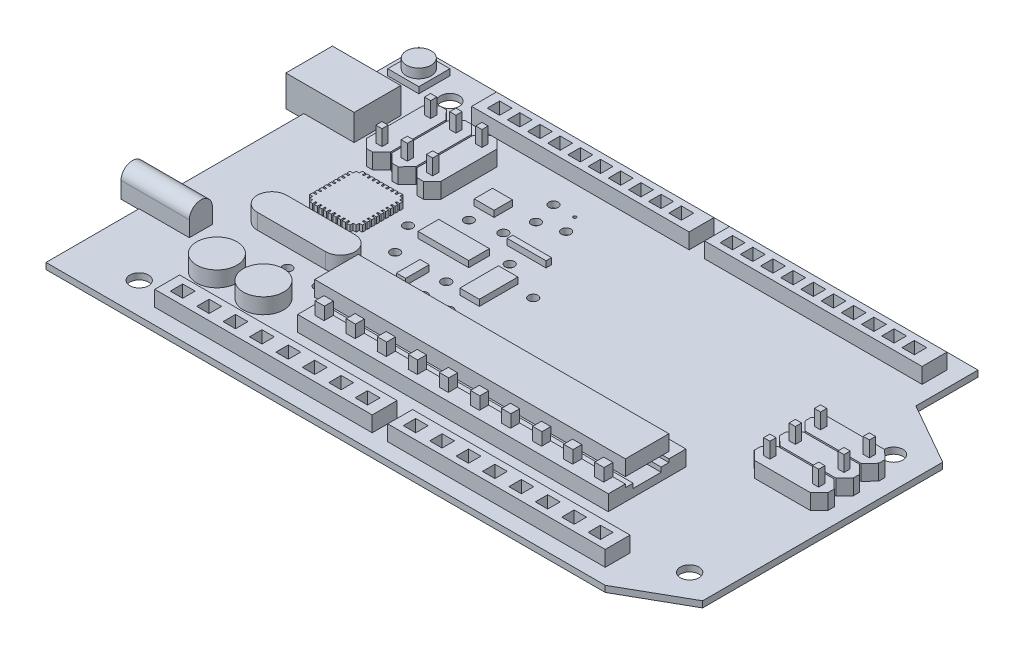
SolidWorks part; units mm, degrees
ref_plane "Front Plane" through (0, 0, 0) normal (0, 0, 1) x (1, 0, 0)
ref_plane "Top Plane" through (0, 0, 0) normal (0, 1, 0) x (1, 0, 0)
ref_plane "Right Plane" through (0, 0, 0) normal (1, 0, 0) x (0, 0, -1)
sketch "Sketch2" plane through (0, 0, 0) normal (0, 1, 0) x (1, 0, 0)
  line L0 (-134.1935, 60.9677) -> (-134.1935, -59.0323)
  line L1 (-134.1935, -59.0323) -> (45.8065, -59.0323)
  line L2 (45.8065, -59.0323) -> (65.8065, -47.6744)
  line L3 (65.8065, -47.6744) -> (65.8065, 29.6099)
  line L4 (65.8065, 29.6099) -> (45.8065, 40.9677)
  line L5 (45.8065, 40.9677) -> (45.8065, 60.9677)
  line L6 (45.8065, 60.9677) -> (-134.1935, 60.9677)
  dimension "D1" = 120
  dimension "D2" = 180
  dimension "D3" = 200
  dimension "D4" = 180
  dimension "D5" = 20
  dimension "D6" = 23
  dimension "D7" = 23
extrude "Boss-Extrude2" add sketch "Sketch2" along normal blind 2
sketch "Sketch3" plane through (0, 2, 0) normal (0, 1, 0) x (1, 0, 0)
  line L0 (-134.1935, 60.9677) -> (-134.1935, -59.0323) construction
  line L1 (-104.1935, 55.9677) -> (-34.1935, 55.9677)
  line L2 (-104.1935, 55.9677) -> (-104.1935, 47.9677)
  line L3 (-104.1935, 47.9677) -> (-34.1935, 47.9677)
  line L4 (-34.1935, 55.9677) -> (-34.1935, 47.9677)
  line L5 (-29.1935, 55.9677) -> (40.8065, 55.9677)
  line L6 (-29.1935, 55.9677) -> (-29.1935, 47.9677)
  line L7 (-29.1935, 47.9677) -> (40.8065, 47.9677)
  line L8 (40.8065, 55.9677) -> (40.8065, 47.9677)
  line L9 (45.8065, 40.9677) -> (45.8065, 60.9677) construction
  line L10 (45.8065, 60.9677) -> (-134.1935, 60.9677) construction
  dimension "D1" = 30
  dimension "D2" = 5
  dimension "D3" = 70
  dimension "D4" = 70
  dimension "D5" = 5
  dimension "D6" = 5
  dimension "D7" = 5
  dimension "D8" = 8
  dimension "D9" = 8
extrude "Boss-Extrude3" add sketch "Sketch3" along normal blind 5
sketch "Sketch4" plane through (0, 7, 0) normal (0, 1, 0) x (1, 0, 0)
  line L0 (-34.1935, 55.9677) -> (-104.1935, 55.9677) construction
  line L1 (-101.1935, 53.9677) -> (-97.1935, 53.9677)
  line L2 (-101.1935, 53.9677) -> (-101.1935, 49.9677)
  line L3 (-101.1935, 49.9677) -> (-97.1935, 49.9677)
  line L4 (-97.1935, 53.9677) -> (-97.1935, 49.9677)
  line L5 (-104.1935, 47.9677) -> (-34.1935, 47.9677) construction
  line L6 (-104.1935, 55.9677) -> (-104.1935, 47.9677) construction
  dimension "D1" = 4
  dimension "D2" = 4
  dimension "D3" = 2
  dimension "D4" = 2
  dimension "D5" = 3
sketch "Sketch5" plane through (0, 7, 0) normal (0, 1, 0) x (1, 0, 0)
  line L0 (40.8065, 55.9677) -> (-29.1935, 55.9677) construction
  line L1 (-26.1935, 53.9677) -> (-22.1935, 53.9677)
  line L2 (-26.1935, 53.9677) -> (-26.1935, 49.9677)
  line L3 (-26.1935, 49.9677) -> (-22.1935, 49.9677)
  line L4 (-22.1935, 53.9677) -> (-22.1935, 49.9677)
  line L5 (-29.1935, 55.9677) -> (-29.1935, 47.9677) construction
  dimension "D1" = 4
  dimension "D2" = 4
  dimension "D3" = 2
  dimension "D4" = 3
extrude "Cut-Extrude1" cut sketch "Sketch4" against normal blind 4
pattern_linear "LPattern3" count 10 spacing 6.5 along (1, 0, 0) of "Cut-Extrude1"
extrude "Cut-Extrude2" cut sketch "Sketch5" against normal blind 4
pattern_linear "LPattern4" count 10 spacing 6.5 along (1, 0, 0) of "Cut-Extrude2"
sketch "Sketch6" plane through (0, 2, 0) normal (0, 1, 0) x (1, 0, 0)
  line L0 (-134.1935, 60.9677) -> (-134.1935, -59.0323) construction
  line L1 (-104.1935, -46.0323) -> (-34.1935, -46.0323)
  line L2 (-104.1935, -46.0323) -> (-104.1935, -54.0323)
  line L3 (-104.1935, -54.0323) -> (-34.1935, -54.0323)
  line L4 (-34.1935, -46.0323) -> (-34.1935, -54.0323)
  line L5 (-29.1935, -46.0323) -> (40.8065, -46.0323)
  line L6 (-29.1935, -46.0323) -> (-29.1935, -54.0323)
  line L7 (-29.1935, -54.0323) -> (40.8065, -54.0323)
  line L8 (40.8065, -46.0323) -> (40.8065, -54.0323)
  line L9 (-134.1935, -59.0323) -> (45.8065, -59.0323) construction
  point P11 (-29.1935, -50.0323)
  dimension "D1" = 5
  dimension "D2" = 70
  dimension "D3" = 70
  dimension "D4" = 30
  dimension "D5" = 5
  dimension "D6" = 5
  dimension "D7" = 5
  dimension "D8" = 8
  dimension "D9" = 8
extrude "Boss-Extrude7" add sketch "Sketch6" along normal blind 5
sketch "Sketch7" plane through (0, 7, 0) normal (0, 1, 0) x (1, 0, 0)
  line L0 (-104.1935, -54.0323) -> (-34.1935, -54.0323) construction
  line L1 (-101.1935, -48.0323) -> (-97.1935, -48.0323)
  line L2 (-101.1935, -48.0323) -> (-101.1935, -52.0323)
  line L3 (-101.1935, -52.0323) -> (-97.1935, -52.0323)
  line L4 (-97.1935, -48.0323) -> (-97.1935, -52.0323)
  line L5 (-34.1935, -46.0323) -> (-104.1935, -46.0323) construction
  line L6 (-104.1935, -46.0323) -> (-104.1935, -54.0323) construction
  dimension "D1" = 4
  dimension "D2" = 4
  dimension "D3" = 2
  dimension "D4" = 2
  dimension "D5" = 3
extrude "Cut-Extrude3" cut sketch "Sketch7" against normal blind 4
pattern_linear "LPattern5" count 8 spacing 8.5 along (1, 0, 0) of "Cut-Extrude3"
sketch "Sketch8" plane through (0, 7, 0) normal (0, 1, 0) x (1, 0, 0)
  line L0 (-29.1935, -54.0323) -> (40.8065, -54.0323) construction
  line L1 (-26.1935, -48.0323) -> (-22.1935, -48.0323)
  line L2 (-26.1935, -48.0323) -> (-26.1935, -52.0323)
  line L3 (-26.1935, -52.0323) -> (-22.1935, -52.0323)
  line L4 (-22.1935, -48.0323) -> (-22.1935, -52.0323)
  line L5 (-29.1935, -46.0323) -> (-29.1935, -54.0323) construction
  dimension "D1" = 4
  dimension "D2" = 4
  dimension "D3" = 2
  dimension "D4" = 3
extrude "Cut-Extrude4" cut sketch "Sketch8" against normal blind 4
pattern_linear "LPattern6" count 8 spacing 8.5 along (1, 0, 0) of "Cut-Extrude4"
sketch "Sketch9" plane through (0, 2, 0) normal (0, 1, 0) x (1, 0, 0)
  line L0 (65.8065, -47.6744) -> (65.8065, 29.6099) construction
  line L1 (-104.1935, -46.0323) -> (-104.1935, -54.0323) construction
  line L2 (-104.1935, 55.9677) -> (-104.1935, 47.9677) construction
  line L3 (45.8065, 60.9677) -> (-134.1935, 60.9677) construction
  line L4 (-134.1935, -59.0323) -> (45.8065, -59.0323) construction
  line L5 (65.8065, 29.6099) -> (45.8065, 40.9677) construction
  line L6 (45.8065, -59.0323) -> (65.8065, -47.6744) construction
  circle A0 centre (55.8065, 23.7888) radius 3
  circle A1 centre (55.8065, -41.8533) radius 3
  circle A2 centre (-114.1935, 50.9677) radius 3
  circle A3 centre (-114.1935, -49.0323) radius 3
  dimension "D1" = 6
  dimension "D2" = 6
  dimension "D3" = 6
  dimension "D4" = 6
  dimension "D5" = 10
  dimension "D9" = 10
  dimension "D10" = 10
  dimension "D11" = 10
  dimension "D6" = 10
  dimension "D7" = 10
  dimension "D8" = 10
  dimension "D12" = 10
extrude "Cut-Extrude5" cut sketch "Sketch9" against normal blind 4
sketch "Sketch10" plane through (0, 2, 0) normal (0, 1, 0) x (1, 0, 0)
  line L0 (65.8065, -47.6744) -> (65.8065, 29.6099) construction
  line L1 (-74.1935, -13.0323) -> (25.8065, -13.0323)
  line L2 (-74.1935, -13.0323) -> (-74.1935, -38.0323)
  line L3 (-74.1935, -38.0323) -> (25.8065, -38.0323)
  line L4 (25.8065, -13.0323) -> (25.8065, -38.0323)
  line L5 (40.8065, -46.0323) -> (-29.1935, -46.0323) construction
  dimension "D1" = 40
  dimension "D2" = 8
  dimension "D3" = 25
  dimension "D4" = 100
extrude "Boss-Extrude8" add sketch "Sketch10" along normal blind 5
sketch "Sketch11" plane through (25.8065, 0, 0) normal (1, 0, 0) x (0, 0, -1)
  line L0 (-38.0323, 7) -> (-13.0323, 7) construction
  line L1 (-21.0323, 7) -> (-30.0323, 7)
  line L2 (-21.0323, 7) -> (-21.0323, 4.5)
  line L3 (-21.0323, 4.5) -> (-30.0323, 4.5)
  line L4 (-30.0323, 7) -> (-30.0323, 4.5)
  line L5 (-13.0323, 7) -> (-13.0323, 2) construction
  line L6 (-38.0323, 7) -> (-38.0323, 2) construction
  line L7 (-38.0323, 2) -> (-13.0323, 2) construction
  dimension "D1" = 8
  dimension "D2" = 9
  dimension "D3" = 8
  dimension "D4" = 2.5
  dimension "D5" = 2.5
extrude "Cut-Extrude6" cut sketch "Sketch11" against normal blind 100
sketch "Sketch13" plane through (0, 7, 0) normal (0, 1, 0) x (1, 0, 0)
  line L0 (-74.1935, -13.0323) -> (-74.1935, -21.0323) construction
  line L1 (-71.1935, -15.5323) -> (-68.1935, -15.5323)
  line L2 (-71.1935, -15.5323) -> (-71.1935, -18.5323)
  line L3 (-71.1935, -18.5323) -> (-68.1935, -18.5323)
  line L4 (-68.1935, -15.5323) -> (-68.1935, -18.5323)
  line L5 (-71.1935, -32.5323) -> (-68.1935, -32.5323)
  line L6 (-71.1935, -32.5323) -> (-71.1935, -35.5323)
  line L7 (-71.1935, -35.5323) -> (-68.1935, -35.5323)
  line L8 (-68.1935, -32.5323) -> (-68.1935, -35.5323)
  line L9 (-74.1935, -30.0323) -> (-74.1935, -38.0323) construction
  line L10 (-74.1935, -21.0323) -> (25.8065, -21.0323) construction
  line L11 (25.8065, -13.0323) -> (-74.1935, -13.0323) construction
  line L12 (-74.1935, -30.0323) -> (25.8065, -30.0323) construction
  dimension "D1" = 3
  dimension "D2" = 3
  dimension "D3" = 3
  dimension "D4" = 3
  dimension "D5" = 3
  dimension "D6" = 3
  dimension "D7" = 2.5
  dimension "D8" = 2.5
  dimension "D9" = 2.5
extrude "Cut-Extrude7" cut sketch "Sketch13" against normal blind 4
pattern_linear "LPattern7" count 10 spacing 10 along (1, 0, 0) of "Cut-Extrude7"
sketch "Sketch15" plane through (0, 3, 0) normal (0, 1, 0) x (1, 0, 0)
  line L0 (-68.1935, -18.5323) -> (-68.1935, -15.5323) construction
  line L1 (-71.1935, -15.5323) -> (-68.1935, -15.5323)
  line L2 (-71.1935, -15.5323) -> (-71.1935, -18.5323)
  line L3 (-71.1935, -18.5323) -> (-68.1935, -18.5323)
  line L4 (-68.1935, -15.5323) -> (-68.1935, -18.5323)
  line L5 (-71.1935, -18.5323) -> (-68.1935, -18.5323) construction
  line L6 (-68.1935, -35.5323) -> (-68.1935, -32.5323) construction
  line L7 (-71.1935, -32.5323) -> (-68.1935, -32.5323)
  line L8 (-71.1935, -32.5323) -> (-71.1935, -35.4)
  line L9 (-71.1935, -35.4) -> (-68.1935, -35.4)
  line L10 (-68.1935, -32.5323) -> (-68.1935, -35.4)
extrude "Boss-Extrude9" add sketch "Sketch15" along normal blind 8
pattern_linear "LPattern8" count 10 spacing 10 along (1, 0, 0) of "Boss-Extrude9"
sketch "Sketch17" plane through (0, 7, 0) normal (0, 1, 0) x (1, 0, 0)
  line L0 (-74.1935, -13.0323) -> (-74.1935, -21.0323) construction
  line L1 (-74.1935, -18.5318) -> (25.8065, -18.5318)
  line L2 (-74.1935, -18.5318) -> (-74.1935, -32.5436)
  line L3 (-74.1935, -32.5436) -> (25.8065, -32.5436)
  line L4 (25.8065, -18.5318) -> (25.8065, -32.5436)
  line L5 (25.8065, -38.0323) -> (25.8065, -30.0323) construction
extrude "Boss-Extrude10" add sketch "Sketch17" along normal blind 7 and the other way blind 1
sketch "Sketch18" plane through (25.8065, 0, 0) normal (1, 0, 0) x (0, 0, -1)
  line L0 (-18.5318, 7) -> (-18.5318, 14) construction
  line L1 (-18.5318, 9.0392) -> (-32.5598, 9.0392)
  line L2 (-18.5318, 9.0392) -> (-18.5318, 5.9657)
  line L3 (-18.5318, 5.9657) -> (-32.5598, 5.9657)
  line L4 (-32.5598, 9.0392) -> (-32.5598, 5.9657)
extrude "Cut-Extrude8" cut sketch "Sketch18" against normal blind 100
sketch "Sketch20" plane through (0, 2, 0) normal (0, 1, 0) x (1, 0, 0)
  line L0 (39.9288, 18.7888) -> (57.9288, 18.7888)
  line L1 (57.9288, 18.7888) -> (60.8065, 16.0105)
  line L2 (60.8065, 16.0105) -> (60.8065, 14.0105)
  line L3 (60.8065, 14.0105) -> (58.0281, 11.1329)
  line L4 (58.0281, 11.1329) -> (40.0281, 11.1329)
  line L5 (40.0281, 11.1329) -> (37.1505, 13.9112)
  line L6 (37.1505, 13.9112) -> (37.1505, 15.9112)
  line L7 (37.1505, 15.9112) -> (39.9288, 18.7888)
  line L8 (65.8065, -47.6744) -> (65.8065, 29.6099) construction
  line L9 (39.9288, 10.6329) -> (57.9288, 10.6329)
  line L10 (57.9288, 10.6329) -> (60.8065, 7.8545)
  line L11 (60.8065, 7.8545) -> (60.8065, 5.8545)
  line L12 (60.8065, 5.8545) -> (58.0281, 2.9769)
  line L13 (58.0281, 2.9769) -> (40.0281, 2.9769)
  line L14 (40.0281, 2.9769) -> (37.1505, 5.7552)
  line L15 (37.1505, 5.7552) -> (37.1505, 7.7552)
  line L16 (37.1505, 7.7552) -> (39.9288, 10.6329)
  line L17 (39.9288, 2.4769) -> (57.9288, 2.4769)
  line L18 (57.9288, 2.4769) -> (60.8065, -0.3015)
  line L19 (60.8065, -0.3015) -> (60.8065, -2.3015)
  line L20 (60.8065, -2.3015) -> (58.0281, -5.1791)
  line L21 (58.0281, -5.1791) -> (40.0281, -5.1791)
  line L22 (40.0281, -5.1791) -> (37.1505, -2.4008)
  line L23 (37.1505, -2.4008) -> (37.1505, -0.4008)
  line L24 (37.1505, -0.4008) -> (39.9288, 2.4769)
  circle A0 centre (55.8065, 23.7888) radius 3 construction
  dimension "D2" = 5
  dimension "D1" = 5
  dimension "D3" = 18
  dimension "D4" = 4
  dimension "D5" = 4
  dimension "D6" = 4
  dimension "D7" = 18
  dimension "D8" = 4
  dimension "D9" = 2
  dimension "D10" = 2
  dimension "D11" = 5
  dimension "D12" = 5
  dimension "D13" = 0.5
  dimension "D14" = 0.5
  dimension "D15" = 4
  dimension "D16" = 4
  dimension "D17" = 2
  dimension "D18" = 2
  dimension "D19" = 4
  dimension "D20" = 4
  dimension "D21" = 18
  dimension "D22" = 4
  dimension "D23" = 4
  dimension "D24" = 2
  dimension "D25" = 4
  dimension "D26" = 4
  dimension "D27" = 2
  dimension "D28" = 18
  dimension "D29" = 18
  dimension "D30" = 18
extrude "Boss-Extrude13" add sketch "Sketch20" along normal blind 5
sketch "Sketch21" plane through (0, 7, 0) normal (0, 1, 0) x (1, 0, 0)
  line L0 (37.1505, -0.4008) -> (37.1505, -2.4008) construction
  line L1 (40.1505, 15.9388) -> (42.1505, 15.9388)
  line L2 (40.1505, 15.9388) -> (40.1505, 13.9388)
  line L3 (40.1505, 13.9388) -> (42.1505, 13.9388)
  line L4 (42.1505, 15.9388) -> (42.1505, 13.9388)
  line L5 (40.1505, 7.8329) -> (42.1505, 7.8329)
  line L6 (40.1505, 7.8329) -> (40.1505, 5.8329)
  line L7 (40.1505, 5.8329) -> (42.1505, 5.8329)
  line L8 (42.1505, 7.8329) -> (42.1505, 5.8329)
  line L9 (40.1505, -0.3699) -> (42.1505, -0.3699)
  line L10 (40.1505, -0.3699) -> (40.1505, -2.3699)
  line L11 (40.1505, -2.3699) -> (42.1505, -2.3699)
  line L12 (42.1505, -0.3699) -> (42.1505, -2.3699)
  line L13 (55.8065, 15.9888) -> (57.8065, 15.9888)
  line L14 (55.8065, 15.9888) -> (55.8065, 13.9888)
  line L15 (55.8065, 13.9888) -> (57.8065, 13.9888)
  line L16 (57.8065, 15.9888) -> (57.8065, 13.9888)
  line L17 (55.8065, 7.8329) -> (57.8065, 7.8329)
  line L18 (55.8065, 7.8329) -> (55.8065, 5.8329)
  line L19 (55.8065, 5.8329) -> (57.8065, 5.8329)
  line L20 (57.8065, 7.8329) -> (57.8065, 5.8329)
  line L21 (55.8065, -0.3231) -> (57.8065, -0.3231)
  line L22 (55.8065, -0.3231) -> (55.8065, -2.3231)
  line L23 (55.8065, -2.3231) -> (57.8065, -2.3231)
  line L24 (57.8065, -0.3231) -> (57.8065, -2.3231)
  line L25 (37.1505, 7.7552) -> (37.1505, 5.7552) construction
  line L26 (37.1505, 15.9112) -> (37.1505, 13.9112) construction
  line L27 (60.8065, 14.0105) -> (60.8065, 16.0105) construction
  line L28 (60.8065, 5.8545) -> (60.8065, 7.8545) construction
  line L29 (60.8065, -2.3015) -> (60.8065, -0.3015) construction
  line L30 (57.9288, 2.4769) -> (39.9288, 2.4769) construction
  line L31 (57.9288, 2.4769) -> (39.9288, 2.4769) construction
  line L32 (40.0281, -5.1791) -> (58.0281, -5.1791) construction
  line L33 (57.9288, 18.7888) -> (39.9288, 18.7888) construction
  line L34 (40.0281, 11.1329) -> (58.0281, 11.1329) construction
  line L35 (57.9288, 18.7888) -> (39.9288, 18.7888) construction
  line L36 (57.9288, 10.6329) -> (39.9288, 10.6329) construction
  point P36 (41.1505, -0.3699)
  dimension "D1" = 2
  dimension "D2" = 2
  dimension "D3" = 2
  dimension "D4" = 2
  dimension "D5" = 2
  dimension "D6" = 2
  dimension "D7" = 2
  dimension "D8" = 2
  dimension "D9" = 2
  dimension "D10" = 2
  dimension "D11" = 2
  dimension "D12" = 3
  dimension "D13" = 3
  dimension "D14" = 3
  dimension "D15" = 2
  dimension "D16" = 3
  dimension "D17" = 3
  dimension "D18" = 3
  dimension "D19" = 2.8468
  dimension "D20" = 2.8468
  dimension "D21" = 2.8092
  dimension "D22" = 2.85
  dimension "D23" = 2.806
  dimension "D24" = 2.8
  dimension "D25" = 2.8
  dimension "D26" = 2.8
  dimension "D27" = 2.8
extrude "Boss-Extrude14" add sketch "Sketch21" along normal blind 5
sketch "Sketch22" plane through (0, 2, 0) normal (0, 1, 0) x (1, 0, 0)
  line L0 (-112.1935, 40.1574) -> (-112.1935, 22.1574)
  line L1 (-112.1935, 22.1574) -> (-109.3832, 19.311)
  line L2 (-109.3832, 19.311) -> (-107.3832, 19.311)
  line L3 (-107.3832, 19.311) -> (-104.5368, 22.1213)
  line L4 (-104.5368, 22.1213) -> (-104.5368, 40.1213)
  line L5 (-104.5368, 40.1213) -> (-107.3471, 42.9677)
  line L6 (-107.3471, 42.9677) -> (-109.3471, 42.9677)
  line L7 (-109.3471, 42.9677) -> (-112.1935, 40.1574)
  line L8 (-104.1935, 47.9677) -> (-34.1935, 47.9677) construction
  line L9 (-134.1935, 60.9677) -> (-134.1935, -59.0323) construction
  line L10 (-104.0368, 40.0944) -> (-104.0368, 22.0944)
  line L11 (-104.0368, 22.0944) -> (-101.1634, 19.3116)
  line L12 (-101.1634, 19.3116) -> (-99.1634, 19.3116)
  line L13 (-99.1634, 19.3116) -> (-96.3807, 22.185)
  line L14 (-96.3807, 22.185) -> (-96.3807, 40.185)
  line L15 (-96.3807, 40.185) -> (-99.2541, 42.9677)
  line L16 (-99.2541, 42.9677) -> (-101.2541, 42.9677)
  line L17 (-101.2541, 42.9677) -> (-104.0368, 40.0944)
  line L18 (-95.8807, 40.1242) -> (-95.8807, 22.1242)
  line L19 (-95.8807, 22.1242) -> (-93.0371, 19.311)
  line L20 (-93.0371, 19.311) -> (-91.0371, 19.311)
  line L21 (-91.0371, 19.311) -> (-88.2239, 22.1545)
  line L22 (-88.2239, 22.1545) -> (-88.2239, 40.1545)
  line L23 (-88.2239, 40.1545) -> (-91.0675, 42.9677)
  line L24 (-91.0675, 42.9677) -> (-93.0675, 42.9677)
  line L25 (-93.0675, 42.9677) -> (-95.8807, 40.1242)
  dimension "D1" = 5
  dimension "D2" = 22
  dimension "D3" = 18
  dimension "D4" = 18
  dimension "D5" = 4
  dimension "D6" = 4
  dimension "D7" = 4
  dimension "D8" = 4
  dimension "D9" = 2
  dimension "D10" = 2
  dimension "D11" = 5
  dimension "D12" = 5
  dimension "D13" = 0.5
  dimension "D14" = 0.5
  dimension "D15" = 4
  dimension "D16" = 4
  dimension "D17" = 4
  dimension "D18" = 4
  dimension "D19" = 4
  dimension "D20" = 18
  dimension "D21" = 18
  dimension "D22" = 4
  dimension "D23" = 18
  dimension "D24" = 18
  dimension "D25" = 4
  dimension "D26" = 4
  dimension "D27" = 2
  dimension "D28" = 2
  dimension "D29" = 2
extrude "Boss-Extrude15" add sketch "Sketch22" along normal blind 5
sketch "Sketch23" plane through (0, 7, 0) normal (0, 1, 0) x (1, 0, 0)
  line L0 (-107.3471, 42.9677) -> (-109.3471, 42.9677) construction
  line L1 (-109.3935, 39.9677) -> (-107.3935, 39.9677)
  line L2 (-109.3935, 39.9677) -> (-109.3935, 37.9677)
  line L3 (-109.3935, 37.9677) -> (-107.3935, 37.9677)
  line L4 (-107.3935, 39.9677) -> (-107.3935, 37.9677)
  line L5 (-101.2368, 39.9677) -> (-99.2368, 39.9677)
  line L6 (-101.2368, 39.9677) -> (-101.2368, 37.9677)
  line L7 (-101.2368, 37.9677) -> (-99.2368, 37.9677)
  line L8 (-99.2368, 39.9677) -> (-99.2368, 37.9677)
  line L9 (-93.0807, 40.1677) -> (-91.0807, 40.1677)
  line L10 (-93.0807, 40.1677) -> (-93.0807, 38.1677)
  line L11 (-93.0807, 38.1677) -> (-91.0807, 38.1677)
  line L12 (-91.0807, 40.1677) -> (-91.0807, 38.1677)
  line L13 (-93.0807, 24.311) -> (-91.0807, 24.311)
  line L14 (-93.0807, 24.311) -> (-93.0807, 22.311)
  line L15 (-93.0807, 22.311) -> (-91.0807, 22.311)
  line L16 (-91.0807, 24.311) -> (-91.0807, 22.311)
  line L17 (-101.2368, 24.3116) -> (-99.2368, 24.3116)
  line L18 (-101.2368, 24.3116) -> (-101.2368, 22.3116)
  line L19 (-101.2368, 22.3116) -> (-99.2368, 22.3116)
  line L20 (-99.2368, 24.3116) -> (-99.2368, 22.3116)
  line L21 (-109.3935, 24.311) -> (-107.3935, 24.311)
  line L22 (-109.3935, 24.311) -> (-109.3935, 22.311)
  line L23 (-109.3935, 22.311) -> (-107.3935, 22.311)
  line L24 (-107.3935, 24.311) -> (-107.3935, 22.311)
  line L25 (-112.1935, 40.1574) -> (-112.1935, 22.1574) construction
  line L26 (-104.5368, 22.1213) -> (-104.5368, 40.1213) construction
  line L27 (-99.2541, 42.9677) -> (-101.2541, 42.9677) construction
  line L28 (-104.0368, 40.0944) -> (-104.0368, 22.0944) construction
  line L29 (-95.8807, 40.1242) -> (-95.8807, 22.1242) construction
  line L30 (-91.0675, 42.9677) -> (-93.0675, 42.9677) construction
  line L31 (-109.3832, 19.311) -> (-107.3832, 19.311) construction
  line L32 (-101.1634, 19.3116) -> (-99.1634, 19.3116) construction
  line L33 (-93.0371, 19.311) -> (-91.0371, 19.311) construction
  dimension "D1" = 2
  dimension "D2" = 2
  dimension "D3" = 3
  dimension "D4" = 2.8
  dimension "D5" = 2.8567
  dimension "D6" = 2
  dimension "D7" = 2
  dimension "D8" = 3
  dimension "D9" = 2.8
  dimension "D10" = 2
  dimension "D11" = 2
  dimension "D12" = 2.8
  dimension "D13" = 2.8
  dimension "D14" = 2
  dimension "D15" = 2
  dimension "D16" = 3
  dimension "D17" = 2.8
  dimension "D18" = 2
  dimension "D19" = 2.8
  dimension "D20" = 2
  dimension "D21" = 3
  dimension "D22" = 2.8
  dimension "D23" = 2
  dimension "D24" = 2
  dimension "D25" = 3
extrude "Boss-Extrude16" add sketch "Sketch23" along normal blind 5
sketch "Sketch24" plane through (0, 2, 0) normal (0, 1, 0) x (1, 0, 0)
  line L0 (-101.1634, 19.3116) -> (-99.1634, 19.3116) construction
  line L1 (-107.6935, 14.3116) -> (-92.6935, 14.3116)
  line L2 (-107.6935, 14.3116) -> (-107.6935, -0.6884)
  line L3 (-107.6935, -0.6884) -> (-92.6935, -0.6884)
  line L4 (-92.6935, 14.3116) -> (-92.6935, -0.6884)
  line L5 (-134.1935, 60.9677) -> (-134.1935, -59.0323) construction
  dimension "D1" = 5
  dimension "D2" = 26.5
  dimension "D3" = 15
  dimension "D4" = 15
extrude "Boss-Extrude17" add sketch "Sketch24" along normal blind 2
sketch "Sketch26" plane through (0, 2, 0) normal (0, 1, 0) x (1, 0, 0)
  line L0 (-92.6935, 14.3116) -> (-107.6935, 14.3116) construction
  line L1 (-106.6935, 14.3116) -> (-105.6935, 14.3116)
  line L2 (-106.6935, 14.3116) -> (-106.6935, 15.3116)
  line L3 (-106.6935, 15.3116) -> (-105.6935, 15.3116)
  line L4 (-105.6935, 14.3116) -> (-105.6935, 15.3116)
  dimension "D1" = 1
  dimension "D2" = 1
  dimension "D3" = 1
extrude "Boss-Extrude19" add sketch "Sketch26" along normal blind 2
pattern_linear "LPattern9" count 9 spacing 1.5 along (1, 0, 0) of "Boss-Extrude19"
sketch "Sketch27" plane through (0, 2, 0) normal (0, 1, 0) x (1, 0, 0)
  line L0 (-107.6935, -0.6884) -> (-92.6935, -0.6884) construction
  line L1 (-106.6935, -0.6884) -> (-105.6935, -0.6884)
  line L2 (-106.6935, -0.6884) -> (-106.6935, -1.6884)
  line L3 (-106.6935, -1.6884) -> (-105.6935, -1.6884)
  line L4 (-105.6935, -0.6884) -> (-105.6935, -1.6884)
  dimension "D1" = 1
  dimension "D2" = 1
  dimension "D3" = 1
extrude "Boss-Extrude20" add sketch "Sketch27" along normal blind 2
pattern_linear "LPattern10" count 9 spacing 1.5 along (1, 0, 0) of "Boss-Extrude20"
sketch "Sketch28" plane through (0, 2, 0) normal (0, 1, 0) x (1, 0, 0)
  line L0 (-92.6935, -0.6884) -> (-92.6935, 14.3116) construction
  line L1 (-92.6935, 13.3116) -> (-91.6935, 13.3116)
  line L2 (-92.6935, 13.3116) -> (-92.6935, 12.3116)
  line L3 (-92.6935, 12.3116) -> (-91.6935, 12.3116)
  line L4 (-91.6935, 13.3116) -> (-91.6935, 12.3116)
  line L5 (-92.6935, 11.8116) -> (-92.6935, 10.8116)
  line L6 (-92.6935, 11.8116) -> (-91.6935, 11.8116)
  line L7 (-91.6935, 11.8116) -> (-91.6935, 10.8116)
  line L8 (-92.6935, 10.8116) -> (-91.6935, 10.8116)
  line L9 (-92.6935, 10.3116) -> (-92.6935, 9.3116)
  line L10 (-92.6935, 10.3116) -> (-91.6935, 10.3116)
  line L11 (-91.6935, 10.3116) -> (-91.6935, 9.3116)
  line L12 (-92.6935, 9.3116) -> (-91.6935, 9.3116)
  line L13 (-92.6935, 8.8116) -> (-92.6935, 7.8116)
  line L14 (-92.6935, 8.8116) -> (-91.6935, 8.8116)
  line L15 (-91.6935, 8.8116) -> (-91.6935, 7.8116)
  line L16 (-92.6935, 7.8116) -> (-91.6935, 7.8116)
  line L17 (-92.6935, 7.3116) -> (-92.6935, 6.3116)
  line L18 (-92.6935, 7.3116) -> (-91.6935, 7.3116)
  line L19 (-91.6935, 7.3116) -> (-91.6935, 6.3116)
  line L20 (-92.6935, 6.3116) -> (-91.6935, 6.3116)
  line L21 (-92.6935, 5.8116) -> (-92.6935, 4.8116)
  line L22 (-92.6935, 5.8116) -> (-91.6935, 5.8116)
  line L23 (-91.6935, 5.8116) -> (-91.6935, 4.8116)
  line L24 (-92.6935, 4.8116) -> (-91.6935, 4.8116)
  line L25 (-92.6935, 4.3116) -> (-92.6935, 3.3116)
  line L26 (-92.6935, 4.3116) -> (-91.6935, 4.3116)
  line L27 (-91.6935, 4.3116) -> (-91.6935, 3.3116)
  line L28 (-92.6935, 3.3116) -> (-91.6935, 3.3116)
  line L29 (-92.6935, 2.8116) -> (-92.6935, 1.8116)
  line L30 (-92.6935, 2.8116) -> (-91.6935, 2.8116)
  line L31 (-91.6935, 2.8116) -> (-91.6935, 1.8116)
  line L32 (-92.6935, 1.8116) -> (-91.6935, 1.8116)
  line L33 (-92.6935, 1.3116) -> (-92.6935, 0.3116)
  line L34 (-92.6935, 1.3116) -> (-91.6935, 1.3116)
  line L35 (-91.6935, 1.3116) -> (-91.6935, 0.3116)
  line L36 (-92.6935, 0.3116) -> (-91.6935, 0.3116)
  dimension "D1" = 1
  dimension "D2" = 1
  dimension "D3" = 1
  dimension "D4" = 9
extrude "Boss-Extrude24" add sketch "Sketch28" along normal blind 2
sketch "Sketch31" plane through (0, 2, 0) normal (0, 1, 0) x (1, 0, 0)
  line L0 (-107.6935, 14.3116) -> (-107.6935, -0.6884) construction
  line L1 (-107.6935, 13.3116) -> (-108.6935, 13.3116)
  line L2 (-107.6935, 13.3116) -> (-107.6935, 12.3116)
  line L3 (-107.6935, 12.3116) -> (-108.6935, 12.3116)
  line L4 (-108.6935, 13.3116) -> (-108.6935, 12.3116)
  line L5 (-107.6935, 11.8116) -> (-107.6935, 10.8116)
  line L6 (-107.6935, 11.8116) -> (-108.6935, 11.8116)
  line L7 (-108.6935, 11.8116) -> (-108.6935, 10.8116)
  line L8 (-107.6935, 10.8116) -> (-108.6935, 10.8116)
  line L9 (-107.6935, 10.3116) -> (-107.6935, 9.3116)
  line L10 (-107.6935, 10.3116) -> (-108.6935, 10.3116)
  line L11 (-108.6935, 10.3116) -> (-108.6935, 9.3116)
  line L12 (-107.6935, 9.3116) -> (-108.6935, 9.3116)
  line L13 (-107.6935, 8.8116) -> (-107.6935, 7.8116)
  line L14 (-107.6935, 8.8116) -> (-108.6935, 8.8116)
  line L15 (-108.6935, 8.8116) -> (-108.6935, 7.8116)
  line L16 (-107.6935, 7.8116) -> (-108.6935, 7.8116)
  line L17 (-107.6935, 7.3116) -> (-107.6935, 6.3116)
  line L18 (-107.6935, 7.3116) -> (-108.6935, 7.3116)
  line L19 (-108.6935, 7.3116) -> (-108.6935, 6.3116)
  line L20 (-107.6935, 6.3116) -> (-108.6935, 6.3116)
  line L21 (-107.6935, 5.8116) -> (-107.6935, 4.8116)
  line L22 (-107.6935, 5.8116) -> (-108.6935, 5.8116)
  line L23 (-108.6935, 5.8116) -> (-108.6935, 4.8116)
  line L24 (-107.6935, 4.8116) -> (-108.6935, 4.8116)
  line L25 (-107.6935, 4.3116) -> (-107.6935, 3.3116)
  line L26 (-107.6935, 4.3116) -> (-108.6935, 4.3116)
  line L27 (-108.6935, 4.3116) -> (-108.6935, 3.3116)
  line L28 (-107.6935, 3.3116) -> (-108.6935, 3.3116)
  line L29 (-107.6935, 2.8116) -> (-107.6935, 1.8116)
  line L30 (-107.6935, 2.8116) -> (-108.6935, 2.8116)
  line L31 (-108.6935, 2.8116) -> (-108.6935, 1.8116)
  line L32 (-107.6935, 1.8116) -> (-108.6935, 1.8116)
  line L33 (-107.6935, 1.3116) -> (-107.6935, 0.3116)
  line L34 (-107.6935, 1.3116) -> (-108.6935, 1.3116)
  line L35 (-108.6935, 1.3116) -> (-108.6935, 0.3116)
  line L36 (-107.6935, 0.3116) -> (-108.6935, 0.3116)
  dimension "D1" = 1
  dimension "D2" = 1
  dimension "D3" = 1
  dimension "D4" = 9
extrude "Boss-Extrude25" add sketch "Sketch31" along normal blind 2
ref_plane "Plane1" through (-120, 0, 0) normal (1, 0, 0) x (0, 0, -1)
sketch "Sketch33" plane through (-120, 0, 0) normal (1, 0, 0) x (0, 0, -1)
  line L0 (-21.6825, 1.7444) -> (-21.6825, 6.993)
  line L1 (-29.0806, 1.7444) -> (-29.0806, 6.993)
  line L2 (-21.6825, 1.7444) -> (-29.0806, 1.7444)
  arc A0 (-29.0806, 6.993) -> (-21.6825, 6.993) centre (-25.3816, 6.993) cw
extrude "Boss-Extrude26" add sketch "Sketch33" along normal blind 2 and the other way blind 20
sketch "Sketch34" plane through (-140, 0, 0) normal (-1, 0, 0) x (0, 0, 1)
  line L0 (22.8825, 3.2444) -> (27.8806, 3.2444)
  line L1 (27.8806, 3.2444) -> (27.8806, 6.9876)
  line L2 (22.8825, 3.2444) -> (22.8825, 6.9876)
  line L3 (29.0806, 1.7444) -> (21.6825, 1.7444) construction
  line L4 (21.6825, 1.7444) -> (21.6825, 6.993) construction
  line L5 (29.0806, 6.993) -> (29.0806, 1.7444) construction
  arc A0 (22.8825, 6.9876) -> (27.8806, 6.9876) centre (25.3816, 6.9876) cw
  dimension "D2" = 1.2
  dimension "D1" = 1.5
  dimension "D3" = 3.7432
  dimension "D4" = 1.2
  dimension "D5" = 4.9981
extrude "Cut-Extrude9" cut sketch "Sketch34" against normal blind 15
sketch "Sketch35" plane through (-120, 0, 0) normal (1, 0, 0) x (0, 0, -1)
  line L1 (38.9677, 0.4127) -> (23.9677, 0.4127)
  line L2 (38.9677, 0.4127) -> (38.9677, 10.4127)
  line L3 (38.9677, 10.4127) -> (23.9677, 10.4127)
  line L4 (23.9677, 0.4127) -> (23.9677, 10.4127)
  dimension "D1" = 10
  dimension "D2" = 15
  dimension "D3" = 22
extrude "Boss-Extrude27" add sketch "Sketch35" along normal blind 2 and the other way blind 20
sketch "Sketch36" plane through (-140, 0, 0) normal (-1, 0, 0) x (0, 0, 1)
  line L0 (-35.4677, 1.9127) -> (-27.4677, 1.9127)
  line L1 (-27.4677, 1.9127) -> (-27.4677, 6.5503)
  line L2 (-27.4677, 6.5503) -> (-29.5586, 8.4127)
  line L3 (-29.5586, 8.4127) -> (-33.6054, 8.4127)
  line L4 (-33.6054, 8.4127) -> (-35.4677, 6.3219)
  line L5 (-35.4677, 6.3219) -> (-35.4677, 1.9127)
  line L6 (-23.9677, 0.4127) -> (-38.9677, 0.4127) construction
  line L7 (-38.9677, 0.4127) -> (-38.9677, 10.4127) construction
  line L8 (-23.9677, 10.4127) -> (-23.9677, 0.4127) construction
  line L9 (-38.9677, 10.4127) -> (-23.9677, 10.4127) construction
  dimension "D1" = 1.5
  dimension "D2" = 3.5
  dimension "D3" = 3.5
  dimension "D4" = 8
  dimension "D5" = 2
  dimension "D6" = 2.8
  dimension "D7" = 2.8
extrude "Cut-Extrude10" cut sketch "Sketch36" against normal blind 20
sketch "Sketch37" plane through (-120, 0, 0) normal (-1, 0, 0) x (0, 0, 1)
  line L0 (-35.4677, 1.9127) -> (-27.4677, 1.9127) construction
  line L1 (-32.4677, 5.9127) -> (-30.4677, 5.9127)
  line L2 (-32.4677, 5.9127) -> (-32.4677, 3.9127)
  line L3 (-32.4677, 3.9127) -> (-30.4677, 3.9127)
  line L4 (-30.4677, 5.9127) -> (-30.4677, 3.9127)
  line L5 (-29.5586, 8.4127) -> (-33.6054, 8.4127) construction
  line L6 (-35.4677, 6.3219) -> (-35.4677, 1.9127) construction
  line L7 (-27.4677, 1.9127) -> (-27.4677, 6.5503) construction
  point P6 (-31.4677, 1.9127)
  dimension "D1" = 2
  dimension "D2" = 2
  dimension "D3" = 2
  dimension "D4" = 2.5
  dimension "D5" = 3
  dimension "D6" = 3
extrude "Boss-Extrude28" add sketch "Sketch37" along normal blind 18
sketch "Sketch38" plane through (0, 2, 0) normal (0, 1, 0) x (1, 0, 0)
  line L0 (-74.1935, -13.0323) -> (-74.1935, -38.0323) construction
  line L1 (-34.1935, -46.0323) -> (-104.1935, -46.0323) construction
  circle A0 centre (-104.1935, -34.0323) radius 6.5
  circle A1 centre (-89.1935, -34.0323) radius 6.5
  dimension "D2" = 13
  dimension "D3" = 13
  dimension "D5" = 12
  dimension "D1" = 15
  dimension "D4" = 15
extrude "Boss-Extrude29" add sketch "Sketch38" along normal blind 5
sketch "Sketch39" plane through (0, 2, 0) normal (0, 1, 0) x (1, 0, 0)
  line L0 (-109.1935, -11.3019) -> (-87.1935, -11.3019) construction
  line L1 (-109.1935, -6.5715) -> (-87.1935, -6.5715)
  line L2 (-109.1935, -16.0323) -> (-87.1935, -16.0323)
  line L3 (-134.1935, 23.9677) -> (-134.1935, -21.6825) construction
  line L4 (-74.1935, -13.0323) -> (-74.1935, -38.0323) construction
  arc A0 (-109.1935, -6.5715) -> (-109.1935, -16.0323) centre (-109.1935, -11.3019) ccw
  arc A1 (-87.1935, -16.0323) -> (-87.1935, -6.5715) centre (-87.1935, -11.3019) ccw
  circle A2 centre (-104.1935, -34.0323) radius 6.5 construction
  point P2 (-98.1935, -11.3019)
  dimension "D2" = 25
  dimension "D1" = 18
  dimension "D3" = 13
extrude "Boss-Extrude30" add sketch "Sketch39" along normal blind 5
sketch "Sketch40" plane through (0, 2, 0) normal (0, 1, 0) x (1, 0, 0)
  line L1 (-81.0004, 14.1819) -> (-64.6823, 14.1819)
  line L2 (-81.0004, 14.1819) -> (-81.0004, 7.5188)
  line L3 (-81.0004, 7.5188) -> (-64.6823, 7.5188)
  line L4 (-64.6823, 14.1819) -> (-64.6823, 7.5188)
  line L5 (-72.8413, 0) -> (-69.8758, 0)
  line L6 (-72.8413, 0) -> (-72.8413, -7.5831)
  line L7 (-72.8413, -7.5831) -> (-69.8758, -7.5831)
  line L8 (-69.8758, 0) -> (-69.8758, -7.5831)
  line L9 (-81.0004, 31.5033) -> (-74.6037, 31.5033)
  line L10 (-81.0004, 31.5033) -> (-81.0004, 25.6187)
  line L11 (-81.0004, 25.6187) -> (-74.6037, 25.6187)
  line L12 (-74.6037, 31.5033) -> (-74.6037, 25.6187)
  line L13 (-64.6823, 21.6755) -> (-52.181, 21.6755)
  line L14 (-64.6823, 21.6755) -> (-64.6823, 19.9031)
  line L15 (-64.6823, 19.9031) -> (-52.181, 19.9031)
  line L16 (-52.181, 21.6755) -> (-52.181, 19.9031)
  line L17 (-58.4316, 10.8503) -> (-52.181, 10.8503)
  line L18 (-58.4316, 10.8503) -> (-58.4316, -1.5612)
  line L19 (-58.4316, -1.5612) -> (-52.181, -1.5612)
  line L20 (-52.181, 10.8503) -> (-52.181, -1.5612)
extrude "Boss-Extrude31" add sketch "Sketch40" along normal blind 2
sketch "Sketch41" plane through (0, 2, 0) normal (0, 1, 0) x (1, 0, 0)
  circle A0 centre (-68.5801, 38.7179) radius 1.5
  circle A1 centre (-66.5904, 31.0672) radius 1.5
  circle A2 centre (-61.7186, 38.7179) radius 0.4913
  circle A3 centre (-59.0742, 33.2698) radius 1.5
  circle A4 centre (-68.793, 22.7983) radius 1.5
  circle A5 centre (-77.9182, 20.8242) radius 1.5
  circle A6 centre (-86.1885, 9.492) radius 1.5
  circle A7 centre (-64.3879, 0) radius 1.5
  circle A8 centre (-64.3879, -7.5265) radius 1.5
  circle A9 centre (-56.1359, -7.5265) radius 1.5
  circle A10 centre (-80.8181, 0) radius 1.5
  circle A11 centre (-59.0742, 15.1182) radius 1.5
  circle A12 centre (-45.8931, 9.492) radius 1.5
  circle A13 centre (-83.7391, -21.7552) radius 1.5
  circle A14 centre (-93.7487, -21.7552) radius 1.5
  dimension "D1" = 3
  dimension "D2" = 3
  dimension "D3" = 3
  dimension "D4" = 3
  dimension "D5" = 3
  dimension "D6" = 3
  dimension "D7" = 3
  dimension "D8" = 3
  dimension "D9" = 3
  dimension "D10" = 3
  dimension "D11" = 3
  dimension "D12" = 3
  dimension "D13" = 3
  dimension "D14" = 3
extrude "Cut-Extrude11" cut sketch "Sketch41" against normal blind 3
sketch "Sketch42" plane through (0, 2, 0) normal (0, 1, 0) x (1, 0, 0)
  line L0 (-134.1935, 60.9677) -> (-134.1935, 38.9677) construction
  line L1 (-131.1935, 57.9677) -> (-121.1935, 57.9677)
  line L2 (-131.1935, 57.9677) -> (-131.1935, 47.9677)
  line L3 (-131.1935, 47.9677) -> (-121.1935, 47.9677)
  line L4 (-121.1935, 57.9677) -> (-121.1935, 47.9677)
  line L5 (45.8065, 60.9677) -> (-134.1935, 60.9677) construction
  dimension "D1" = 10
  dimension "D2" = 10
  dimension "D3" = 3
  dimension "D4" = 3
extrude "Boss-Extrude32" add sketch "Sketch42" along normal blind 2
sketch "Sketch43" plane through (0, 4, 0) normal (0, 1, 0) x (1, 0, 0)
  line L0 (-131.1935, 47.9677) -> (-121.1935, 47.9677) construction
  line L1 (-131.1935, 57.9677) -> (-131.1935, 47.9677) construction
  circle A0 centre (-126.1935, 52.9677) radius 4
  dimension "D1" = 8
  dimension "D2" = 5
  dimension "D3" = 5
extrude "Boss-Extrude33" add sketch "Sketch43" along normal blind 3
